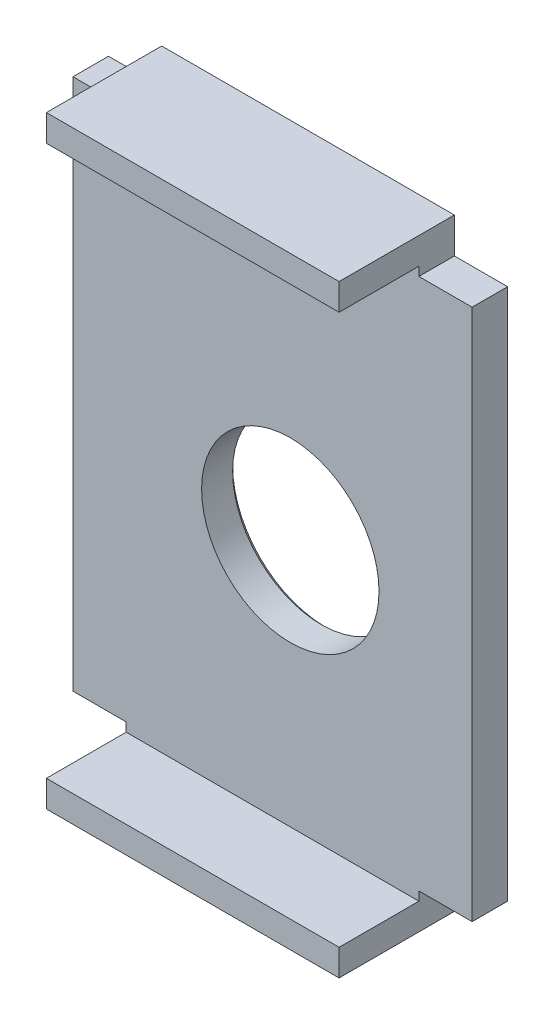
SolidWorks part; units mm, degrees
ref_plane "Front Plane" through (0, 0, 0) normal (0, 0, 1) x (1, 0, 0)
ref_plane "Top Plane" through (0, 0, 0) normal (0, 1, 0) x (1, 0, 0)
ref_plane "Right Plane" through (0, 0, 0) normal (1, 0, 0) x (0, 0, -1)
sketch "Sketch1" plane through (0, 0, 0) normal (0, 0, 1) x (1, 0, 0)
  line L5 (-22.5, -30) -> (22.5, -30)
  line L6 (-22.5, -30) -> (-22.5, 30)
  line L7 (-22.5, 30) -> (22.5, 30)
  line L8 (22.5, -30) -> (22.5, 30)
  line L9 (-22.5, -30) -> (22.5, 30) construction
  line L10 (-22.5, 30) -> (22.5, -30) construction
  circle A2 centre (2, -3) radius 10
  point P0 (0, 0)
  point P5 (2, -8.3235)
  dimension "D3" = 20
  dimension "D4" = 20.5
  dimension "D1" = 60
  dimension "D2" = 45
  dimension "D5" = 3
extrude "Boss-Extrude1" add sketch "Sketch1" along normal mid plane 4
sketch "Sketch3" plane through (0, 0, -2) normal (0, 0, -1) x (-1, 0, 0)
  line L0 (-22.5, 30) -> (22.5, 30) construction
  line L1 (-16.5, 30) -> (16.5, 30)
  line L2 (-16.5, 30) -> (-16.5, 34)
  line L3 (-16.5, 34) -> (16.5, 34)
  line L4 (16.5, 30) -> (16.5, 34)
  line L5 (-22.5, -30) -> (-22.5, 30) construction
  line L6 (22.5, 30) -> (22.5, -30) construction
  line L7 (22.5, -30) -> (-22.5, -30) construction
  line L8 (-16.5, -30) -> (16.5, -30)
  line L9 (-16.5, -30) -> (-16.5, -34)
  line L10 (-16.5, -34) -> (16.5, -34)
  line L11 (16.5, -30) -> (16.5, -34)
  dimension "D1" = 6
  dimension "D2" = 6
  dimension "D3" = 4
extrude "Boss-Extrude3" add sketch "Sketch3" against normal blind 13
chamfer "Chamfer1" distance 0.5 angle 45 1 edges at (12, -3, -2)
sketch "Sketch4" plane through (0, 0, 11) normal (0, 0, 1) x (1, 0, 0)
  line L0 (16.5, 34) -> (16.5, 30) construction
  line L1 (-16.5, 30) -> (16.5, 30)
  line L2 (-16.5, 30) -> (-16.5, 31)
  line L3 (-16.5, 31) -> (16.5, 31)
  line L4 (16.5, 30) -> (16.5, 31)
  line L5 (-16.5, -34) -> (-16.5, -30) construction
  line L6 (16.5, -30) -> (-16.5, -30)
  line L7 (16.5, -30) -> (16.5, -31)
  line L8 (16.5, -31) -> (-16.5, -31)
  line L9 (-16.5, -30) -> (-16.5, -31)
  dimension "D1" = 1
extrude "Cut-Extrude1" cut sketch "Sketch4" against normal up to vertex (9 mm away) up to point (16.5, -30, 2)
equation "\"padding\"=6"
equation "\"wall_thick_ness\"=4"
equation "\"D1@Sketch3\"=\"padding\""
equation "\"D2@Sketch3\"=\"padding\""
equation "\"D3@Sketch3\"=\"wall_thick_ness\""
equation "\"D1@Boss-Extrude1\"=\"wall_thick_ness\""
